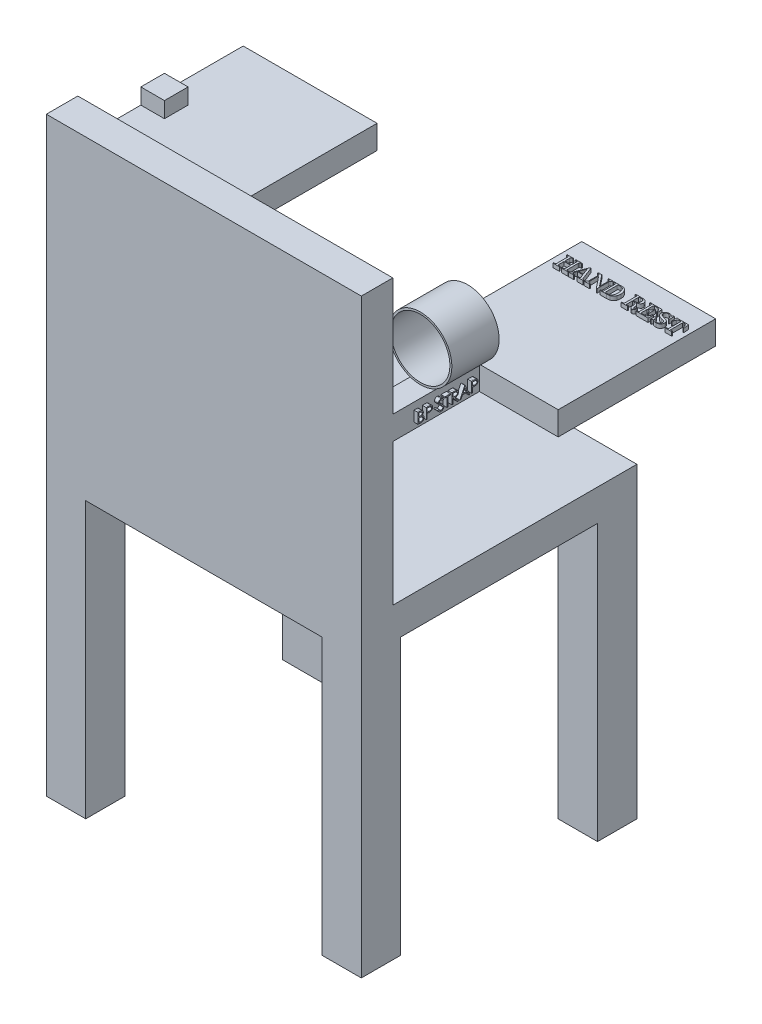
SolidWorks part; units mm, degrees
ref_plane "Front Plane" through (0, 0, 0) normal (0, 0, 1) x (1, 0, 0)
ref_plane "Top Plane" through (0, 0, 0) normal (0, 1, 0) x (1, 0, 0)
ref_plane "Right Plane" through (0, 0, 0) normal (1, 0, 0) x (0, 0, -1)
sketch "Sketch1" plane through (0, 0, 0) normal (1, 0, 0) x (0, 0, -1)
  line L0 (0, 0) -> (0, 40)
  line L1 (0, 40) -> (4, 40)
  line L2 (4, 40) -> (4, 4)
  line L3 (4, 4) -> (35, 4)
  line L4 (35, 4) -> (35, 0)
  line L5 (35, 0) -> (0, 0)
  line L6 (4, 25) -> (35, 25)
  line L7 (35, 22) -> (4, 22)
  line L8 (35, 25) -> (35, 22)
  line L10 (0, 0) -> (5, 0)
  line L11 (0, 0) -> (0, -35)
  line L12 (0, -35) -> (5, -35)
  line L13 (5, 0) -> (5, -35)
  line L14 (35, 0) -> (30, 0)
  line L15 (35, 0) -> (35, -35)
  line L16 (35, -35) -> (30, -35)
  line L17 (30, 0) -> (30, -35)
  dimension "D1" = 4
  dimension "D2" = 4
  dimension "D3" = 35
  dimension "D4" = 40
  dimension "D5" = 31
  dimension "D6" = 3
  dimension "D7" = 15
  dimension "D8" = 5
  dimension "D9" = 35
  dimension "D10" = 35
  dimension "D11" = 5
extrude "Boss-Extrude1" add sketch "Sketch1" against normal blind 40 contours L5 L4 L3 L2 L1 L0 region at (0, 20, -0.5315)
extrude "Boss-Extrude2" add sketch "Sketch1<3>" against normal blind 3 contours L8 L6 L2 L7 region at (0, 23.5, -19.5)
sketch "Sketch1<3>" plane through (0, 0, 0) normal (1, 0, 0) x (0, 0, -1) same geometry as "Sketch1"
extrude "Boss-Extrude3" add sketch "Sketch1<4>" against normal blind 5 contours L13 L5 L11 L12 | L5 L17 L16 L15 region at (0, -17.5, -2.5) region at (0, -17.5, -32.5)
sketch "Sketch1<4>" plane through (0, 0, 0) normal (1, 0, 0) x (0, 0, -1) same geometry as "Sketch1"
sketch "Sketch2" plane through (-40, 0, 0) normal (-1, 0, 0) x (0, 0, 1)
  line L1 (-4, 25) -> (-35, 25)
  line L2 (-4, 25) -> (-4, 22)
  line L3 (-4, 22) -> (-35, 22)
  line L4 (-35, 25) -> (-35, 22)
  line L5 (-35, 0) -> (-30, 0)
  line L6 (-35, 0) -> (-35, -35)
  line L7 (-35, -35) -> (-30, -35)
  line L8 (-30, 0) -> (-30, -35)
  line L9 (-5, 0) -> (0, 0)
  line L10 (-5, 0) -> (-5, -35)
  line L11 (-5, -35) -> (0, -35)
  line L12 (0, 0) -> (0, -35)
  line M1 (-35, 0) -> (0, 0)
  line M4 (-4, 40) -> (-4, 4)
extrude "Boss-Extrude4" add sketch "Sketch2" against normal blind 3 contours L1 L4 L3 M4 region at (-40, 23.5, -19.5)
extrude "Boss-Extrude5" add sketch "Sketch2<3>" against normal blind 5 contours L12 L10 L11 M1 | L8 L6 L7 M1 region at (-40, -17.5, -2.5) region at (-40, -17.5, -32.5)
sketch "Sketch2<3>" plane through (-40, 0, 0) normal (-1, 0, 0) x (0, 0, 1) same geometry as "Sketch2"
sketch "Sketch3" plane through (0, 0, -35) normal (0, 0, -1) x (-1, 0, 0)
  line L0 (0, 25) -> (0, 22) construction
  line L1 (-10, 25) -> (7, 25)
  line L2 (-10, 25) -> (-10, 22)
  line L3 (-10, 22) -> (7, 22)
  line L4 (7, 25) -> (7, 22)
  line L5 (33, 25) -> (50, 25)
  line L6 (33, 25) -> (33, 22)
  line L7 (33, 22) -> (50, 22)
  line L8 (50, 25) -> (50, 22)
  line L9 (40, 25) -> (40, 22) construction
  point P10 (0, 23.5)
  point P13 (40, 23.5)
  dimension "D1" = 7
  dimension "D2" = 10
  dimension "D3" = 7
  dimension "D4" = 10
extrude "Boss-Extrude6" add sketch "Sketch3" against normal blind 20
sketch "Sketch4" plane through (0, 0, -15) normal (0, 0, 1) x (1, 0, 0)
  line L0 (0, 40) -> (0, 25) construction
  line L3 (-3, 25) -> (0, 25) construction
  circle A0 centre (-1.5, 29) radius 4
  circle A2 centre (-1.5, 29) radius 3.75
  point P12 (-1.5, 25)
  dimension "D4" = 8
  dimension "D7" = 7.5
  dimension "D1" = 1.5
  dimension "D3" = 4
extrude "Boss-Extrude7" add sketch "Sketch4" along normal blind 6 separate body
sketch "Sketch5" plane through (0, 25, 0) normal (0, 1, 0) x (1, 0, 0)
  line L0 (-50, 15) -> (-50, 35) construction
  line L1 (-50, 22) -> (-47, 22)
  line L2 (-50, 22) -> (-50, 25)
  line L3 (-50, 25) -> (-47, 25)
  line L4 (-47, 22) -> (-47, 25)
  line L5 (-33, 35) -> (-50, 35) construction
  dimension "D1" = 10
  dimension "D2" = 3
  dimension "D3" = 3
extrude "Boss-Extrude8" add sketch "Sketch5" along normal blind 2
sketch "Sketch6" plane through (0, 25, 0) normal (0, 1, 0) x (1, 0, 0)
  text T0 "HAND REST" font "Century Schoolbook" height in points 7
extrude "Boss-Extrude9" add sketch "Sketch6" along normal blind 0.5
sketch "Sketch7" plane through (0, 0, 0) normal (1, 0, 0) x (0, 0, -1)
  text T0 "BP STRAP" font "Century Gothic" height in points 5
extrude "Boss-Extrude10" add sketch "Sketch7" along normal blind 0.5
sketch "Sketch8" plane through (-50, 0, 0) normal (-1, 0, 0) x (0, 0, 1)
  text T0 "TEMP SENSOR" font "Century Gothic" height in points 6
extrude "Boss-Extrude11" add sketch "Sketch8" along normal blind 0.5
